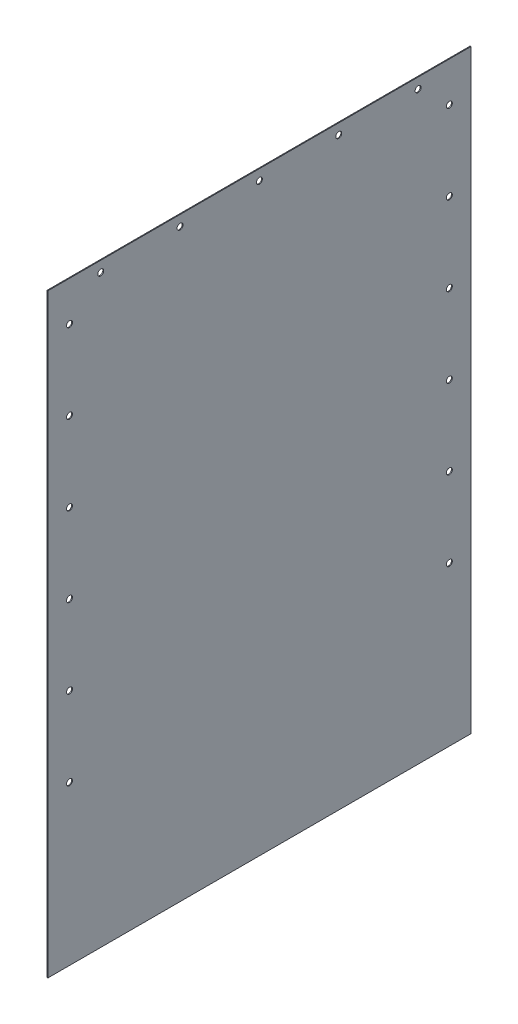
SolidWorks part; units mm, degrees
ref_plane "前视" through (0, 0, 0) normal (0, 0, 1) x (1, 0, 0)
ref_plane "上视" through (0, 0, 0) normal (0, 1, 0) x (1, 0, 0)
ref_plane "右视" through (0, 0, 0) normal (1, 0, 0) x (0, 0, -1)
sketch "Sketch1" plane through (0, 0, 0) normal (1, 0, 0) x (0, 0, -1)
  line L1 (-141.0753, 110.681) -> (178.9247, 110.681)
  line L2 (-141.0753, 110.681) -> (-141.0753, -339.319)
  line L3 (-141.0753, -339.319) -> (178.9247, -339.319)
  line L4 (178.9247, 110.681) -> (178.9247, -339.319)
  dimension "D1" = 320
  dimension "D2" = 450
extrude "Boss-Extrude1" add sketch "Sketch1" along normal blind 0.635
sketch "Sketch2" plane through (0, 0, 0) normal (1, 0, 0) x (0, 0, -1)
  line L2 (-141.0753, 110.681) -> (-141.0753, -339.319) construction
  line L3 (178.9247, 110.681) -> (-141.0753, 110.681) construction
  circle A0 centre (-124.6753, 80.681) radius 2.248
  point P0 (-124.6753, 80.681)
  dimension "D1" = 16.4
  dimension "D2" = 30
  dimension "D3" = 4.496
extrude "Cut-Extrude1" cut sketch "Sketch2" along normal through all
ref_axis "Axis1" through (0.635, 110.681, -18.9247) along (-0.0014, -1, 0)
ref_plane "Plane1" through (0, 0, -18.9247) normal (0, 0, 1) x (-0.0014, -1, 0)
pattern_linear "LPattern1" count 6 spacing 60 along (0, -1, 0) of "Cut-Extrude1"
mirror "Mirror2" about plane through (0, 0, -18.9247) normal (0, 0, 1) of "LPattern1"
sketch "Sketch3" plane through (0, 0, 0) normal (-1, 0, 0) x (0, 0, 1)
  line L0 (-178.9247, 110.681) -> (141.0753, 110.681) construction
  line L1 (-178.9247, -339.319) -> (-178.9247, 110.681) construction
  circle A0 centre (-138.9247, 102.706) radius 2.248
  point P0 (-138.9247, 102.706)
  dimension "D3" = 4.496
  dimension "D1" = 7.975
  dimension "D2" = 40
extrude "Cut-Extrude2" cut sketch "Sketch3" against normal through all contours A0
pattern_linear "LPattern2" count 5 spacing 60 along (0, 0, 1) of "Cut-Extrude2"
